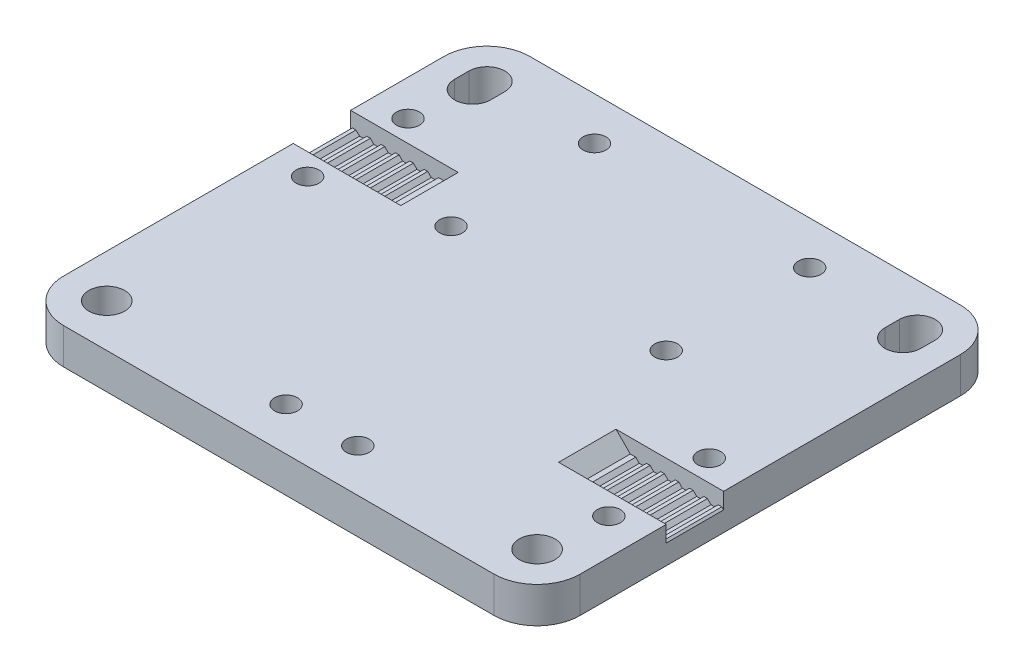
SolidWorks part; units mm, degrees
ref_plane "Front Plane" through (0, 0, 0) normal (0, 0, 1) x (1, 0, 0)
ref_plane "Top Plane" through (0, 0, 0) normal (0, 1, 0) x (1, 0, 0)
ref_plane "Right Plane" through (0, 0, 0) normal (1, 0, 0) x (0, 0, -1)
sketch "Sketch1" plane through (0, 0, 0) normal (0, 1, 0) x (1, 0, 0)
  line L0 (8.5, 59) -> (8.5, 57)
  line L1 (0, 0) -> (72, 0)
  line L2 (0, 0) -> (0, 65)
  line L3 (0, 65) -> (72, 65)
  line L4 (72, 0) -> (72, 65)
  line L5 (3.5, 59) -> (3.5, 57)
  line L6 (36, 65) -> (36, 0) construction
  line L7 (68.5, 59) -> (68.5, 57)
  line L8 (63.5, 59) -> (63.5, 57)
  arc A0 (8.5, 59) -> (3.5, 59) centre (6, 59) ccw
  arc A1 (3.5, 57) -> (8.5, 57) centre (6, 57) ccw
  circle A2 centre (6, 6) radius 2.5
  circle A3 centre (66, 6) radius 2.5
  arc A4 (68.5, 57) -> (63.5, 57) centre (66, 57) cw
  arc A5 (63.5, 59) -> (68.5, 59) centre (66, 59) cw
  circle A6 centre (5, 49) radius 1.6
  circle A7 centre (5, 35) radius 1.6
  circle A8 centre (21, 39) radius 1.6
  circle A9 centre (21, 59) radius 1.6
  circle A10 centre (51, 59) radius 1.6
  circle A11 centre (51, 39) radius 1.6
  circle A12 centre (67, 29) radius 1.6
  circle A13 centre (67, 15) radius 1.6
  circle A14 centre (41, 6) radius 1.6
  circle A15 centre (31, 6) radius 1.6
  dimension "D3" = 5
  dimension "D4" = 5
  dimension "D8" = 5
  dimension "D9" = 6
  dimension "D10" = 6
  dimension "D11" = 3.2
  dimension "D12" = 5
  dimension "D13" = 16
  dimension "D14" = 30
  dimension "D15" = 26
  dimension "D16" = 6
  dimension "D17" = 21
  dimension "D18" = 21
  dimension "D19" = 5
  dimension "D20" = 6
  dimension "D21" = 31
  dimension "D22" = 41
  dimension "D23" = 15
  dimension "D24" = 29
  dimension "D1" = 72
  dimension "D2" = 65
  dimension "D5" = 2
  dimension "D6" = 6
  dimension "D7" = 6
extrude "Boss-Extrude1" add sketch "Sketch1" along normal blind 5
fillet "Fillet1" radius 6 4 edges at (72, 2.5, 0) (72, 2.5, -65) (0, 2.5, -65) (0, 2.5, 0)
sketch "Sketch2" plane through (0, 5, 0) normal (0, 1, 0) x (1, 0, 0)
  line L0 (0, 59) -> (0, 6) construction
  line L1 (0, 46) -> (15, 46)
  line L2 (0, 46) -> (0, 38)
  line L3 (0, 38) -> (15, 38)
  line L4 (15, 46) -> (15, 38)
  line L5 (66, 65) -> (6, 65) construction
  line L6 (72, 6) -> (72, 59) construction
  line L7 (72, 18) -> (57, 18)
  line L8 (72, 18) -> (72, 26)
  line L9 (72, 26) -> (57, 26)
  line L10 (57, 18) -> (57, 26)
  line L11 (6, 0) -> (66, 0) construction
  dimension "D1" = 15
  dimension "D2" = 8
  dimension "D3" = 19
  dimension "D4" = 8
  dimension "D5" = 15
  dimension "D6" = 18
extrude "Cut-Extrude1" cut sketch "Sketch2" against normal blind 2
chamfer "Chamfer1" distance 2 angle 45 2 edges at (57, 3, -22) (15, 3, -42)
sketch "Sketch3" plane through (0, 3, 0) normal (0, 1, 0) x (1, 0, 0)
  line L1 (13, 46) -> (0, 46) construction
  line L2 (1.25, 46) -> (1.75, 46)
  line L3 (1.25, 46) -> (1.25, 38)
  line L4 (1.25, 38) -> (1.75, 38)
  line L8 (1.75, 46) -> (1.75, 38)
  line L9 (0, 38) -> (15, 38) construction
  line L10 (15, 46) -> (0, 46) construction
  line L11 (3.25, 46) -> (3.75, 46)
  line L13 (3.25, 46) -> (3.25, 38)
  line L14 (3.25, 38) -> (3.75, 38)
  line L15 (3.75, 46) -> (3.75, 38)
  line L16 (5.25, 46) -> (5.75, 46)
  line L18 (5.25, 46) -> (5.25, 38)
  line L19 (5.25, 38) -> (5.75, 38)
  line L20 (5.75, 46) -> (5.75, 38)
  line L21 (0, 38) -> (13, 38) construction
  line L23 (11.25, 46) -> (11.75, 46)
  line L24 (11.25, 46) -> (11.25, 38)
  line L25 (11.25, 38) -> (11.75, 38)
  line L26 (7.25, 46) -> (7.75, 46)
  line L27 (7.25, 46) -> (7.25, 38)
  line L28 (7.25, 38) -> (7.75, 38)
  line L29 (7.75, 46) -> (7.75, 38)
  line L30 (0, 46) -> (0, 38) construction
  line L31 (9.25, 46) -> (9.75, 46)
  line L32 (9.25, 46) -> (9.25, 38)
  line L33 (9.25, 38) -> (9.75, 38)
  line L35 (72, 26) -> (59, 26) construction
  line L36 (70.75, 26) -> (70.25, 26)
  line L37 (70.75, 26) -> (70.75, 18)
  line L38 (70.75, 18) -> (70.25, 18)
  line L41 (70.25, 26) -> (70.25, 18)
  line L42 (57, 18) -> (72, 18) construction
  line L43 (72, 18) -> (72, 26) construction
  line L44 (68.75, 26) -> (68.25, 26)
  line L46 (68.75, 26) -> (68.75, 18)
  line L47 (68.75, 18) -> (68.25, 18)
  line L48 (68.25, 26) -> (68.25, 18)
  line L49 (66.75, 26) -> (66.25, 26)
  line L50 (66.75, 26) -> (66.75, 18)
  line L51 (66.75, 18) -> (66.25, 18)
  line L52 (66.25, 26) -> (66.25, 18)
  line L53 (64.75, 26) -> (64.25, 26)
  line L54 (64.75, 26) -> (64.75, 18)
  line L55 (64.75, 18) -> (64.25, 18)
  line L56 (64.25, 26) -> (64.25, 18)
  line L57 (62.75, 26) -> (62.25, 26)
  line L59 (62.75, 26) -> (62.75, 18)
  line L60 (62.75, 18) -> (62.25, 18)
  line L61 (62.25, 26) -> (62.25, 18)
  line L62 (60.75, 26) -> (60.25, 26)
  line L63 (60.75, 26) -> (60.75, 18)
  line L64 (60.75, 18) -> (60.25, 18)
  line L65 (60.25, 26) -> (60.25, 18)
  line L67 (9.75, 46) -> (9.75, 38)
  line L68 (11.75, 46) -> (11.75, 38)
  dimension "D3" = 1.25
  dimension "D4" = 0.5
  dimension "D5" = 1.5
  dimension "D6" = 0.5
  dimension "D7" = 1.5
  dimension "D8" = 0.5
  dimension "D9" = 1.5
  dimension "D10" = 0.5
  dimension "D11" = 0.5
  dimension "D12" = 1.5
  dimension "D13" = 1.5
  dimension "D14" = 0.5
  dimension "D15" = 1.25
  dimension "D16" = 0.5
  dimension "D17" = 1.5
  dimension "D18" = 0.5
  dimension "D19" = 1.5
  dimension "D20" = 0.5
  dimension "D21" = 1.5
  dimension "D22" = 0.5
  dimension "D23" = 1.5
  dimension "D24" = 0.5
  dimension "D25" = 1.5
  dimension "D26" = 0.5
extrude "Cut-Extrude2" cut sketch "Sketch3" against normal blind 0.5
chamfer "Chamfer2" distance 0.5 angle 45 24 edges at (70.75, 3, -22) (70.25, 3, -22) (68.75, 3, -22) (68.25, 3, -22) (66.75, 3, -22) (66.25, 3, -22) (64.75, 3, -22) (64.25, 3, -22) (62.75, 3, -22) (62.25, 3, -22) (60.75, 3, -22) (60.25, 3, -22) (11.75, 3, -42) (11.25, 3, -42) (9.75, 3, -42) (9.25, 3, -42) (7.75, 3, -42) (7.25, 3, -42) (5.75, 3, -42) (5.25, 3, -42) (3.75, 3, -42) (3.25, 3, -42) (1.75, 3, -42) (1.25, 3, -42)
chamfer "Chamfer3" distance 0.25 angle 45 2 edges at (72, 3, -22) (0, 3, -42)
sketch "Sketch4" plane through (0, 0, 0) normal (0, -1, 0) x (1, 0, 0)
  line L1 (8.4064, -49) -> (6.7032, -46.05)
  line L2 (6.7032, -46.05) -> (3.2968, -46.05)
  line L3 (3.2968, -46.05) -> (1.5936, -49)
  line L4 (1.5936, -49) -> (3.2968, -51.95)
  line L5 (3.2968, -51.95) -> (6.7032, -51.95)
  line L6 (6.7032, -51.95) -> (8.4064, -49)
  line L7 (8.4064, -35) -> (6.7032, -32.05)
  line L8 (6.7032, -32.05) -> (3.2968, -32.05)
  line L9 (3.2968, -32.05) -> (1.5936, -35)
  line L10 (1.5936, -35) -> (3.2968, -37.95)
  line L11 (3.2968, -37.95) -> (6.7032, -37.95)
  line L12 (6.7032, -37.95) -> (8.4064, -35)
  line L13 (24.4064, -39) -> (22.7032, -36.05)
  line L14 (22.7032, -36.05) -> (19.2968, -36.05)
  line L15 (19.2968, -36.05) -> (17.5936, -39)
  line L16 (17.5936, -39) -> (19.2968, -41.95)
  line L17 (19.2968, -41.95) -> (22.7032, -41.95)
  line L18 (22.7032, -41.95) -> (24.4064, -39)
  line L19 (54.4064, -39) -> (52.7032, -36.05)
  line L20 (52.7032, -36.05) -> (49.2968, -36.05)
  line L21 (49.2968, -36.05) -> (47.5936, -39)
  line L22 (47.5936, -39) -> (49.2968, -41.95)
  line L23 (49.2968, -41.95) -> (52.7032, -41.95)
  line L24 (52.7032, -41.95) -> (54.4064, -39)
  line L25 (54.4064, -59) -> (52.7032, -56.05)
  line L26 (52.7032, -56.05) -> (49.2968, -56.05)
  line L27 (49.2968, -56.05) -> (47.5936, -59)
  line L28 (47.5936, -59) -> (49.2968, -61.95)
  line L29 (49.2968, -61.95) -> (52.7032, -61.95)
  line L30 (52.7032, -61.95) -> (54.4064, -59)
  line L31 (24.4064, -59) -> (22.7032, -56.05)
  line L32 (22.7032, -56.05) -> (19.2968, -56.05)
  line L33 (19.2968, -56.05) -> (17.5936, -59)
  line L34 (17.5936, -59) -> (19.2968, -61.95)
  line L35 (19.2968, -61.95) -> (22.7032, -61.95)
  line L36 (22.7032, -61.95) -> (24.4064, -59)
  line L37 (34.4064, -6) -> (32.7032, -3.05)
  line L38 (32.7032, -3.05) -> (29.2968, -3.05)
  line L39 (29.2968, -3.05) -> (27.5936, -6)
  line L40 (27.5936, -6) -> (29.2968, -8.95)
  line L41 (29.2968, -8.95) -> (32.7032, -8.95)
  line L42 (32.7032, -8.95) -> (34.4064, -6)
  line L43 (44.4064, -6) -> (42.7032, -3.05)
  line L44 (42.7032, -3.05) -> (39.2968, -3.05)
  line L45 (39.2968, -3.05) -> (37.5936, -6)
  line L46 (37.5936, -6) -> (39.2968, -8.95)
  line L47 (39.2968, -8.95) -> (42.7032, -8.95)
  line L48 (42.7032, -8.95) -> (44.4064, -6)
  line L49 (70.4064, -15) -> (68.7032, -12.05)
  line L50 (68.7032, -12.05) -> (65.2968, -12.05)
  line L51 (65.2968, -12.05) -> (63.5936, -15)
  line L52 (63.5936, -15) -> (65.2968, -17.95)
  line L53 (65.2968, -17.95) -> (68.7032, -17.95)
  line L54 (68.7032, -17.95) -> (70.4064, -15)
  line L55 (70.4064, -29) -> (68.7032, -26.05)
  line L56 (68.7032, -26.05) -> (65.2968, -26.05)
  line L57 (65.2968, -26.05) -> (63.5936, -29)
  line L58 (63.5936, -29) -> (65.2968, -31.95)
  line L59 (65.2968, -31.95) -> (68.7032, -31.95)
  line L60 (68.7032, -31.95) -> (70.4064, -29)
  circle A0 centre (5, -49) radius 2.95 construction
  circle A1 centre (5, -35) radius 2.95 construction
  circle A2 centre (21, -39) radius 2.95 construction
  circle A3 centre (51, -39) radius 2.95 construction
  circle A4 centre (51, -59) radius 2.95 construction
  circle A5 centre (21, -59) radius 2.95 construction
  circle A6 centre (31, -6) radius 2.95 construction
  circle A7 centre (41, -6) radius 2.95 construction
  circle A8 centre (67, -15) radius 2.95 construction
  circle A9 centre (67, -29) radius 2.95 construction
  dimension "D1" = 5.9
  dimension "D2" = 5.9
  dimension "D3" = 5.9
  dimension "D4" = 5.9
  dimension "D5" = 5.9
  dimension "D6" = 5.9
  dimension "D7" = 5.9
  dimension "D8" = 5.9
  dimension "D9" = 5.9
  dimension "D10" = 5.9
extrude "Cut-Extrude3" cut sketch "Sketch4" against normal blind 2.5
